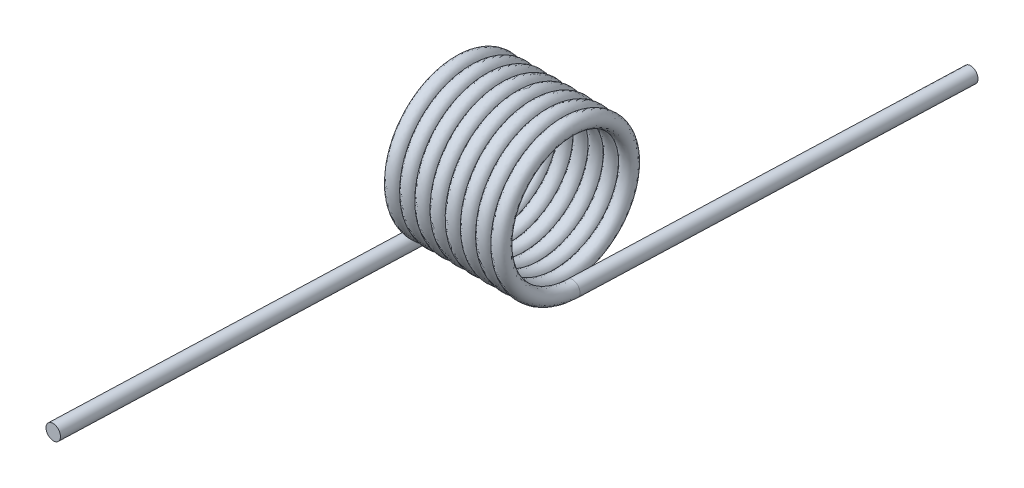
SolidWorks part; units mm, degrees
ref_plane "Front" through (0, 0, 0) normal (0, 0, 1) x (1, 0, 0)
ref_plane "Top" through (0, 0, 0) normal (0, 1, 0) x (1, 0, 0)
ref_plane "Right" through (0, 0, 0) normal (1, 0, 0) x (0, 0, -1)
sketch "Sketch1" plane through (0, 0, 0) normal (1, 0, 0) x (0, 0, -1)
  line L0 (0, 0) -> (0, -7.9375) construction
  line L1 (0, -7.9375) -> (0, -8.9281) construction
  line L2 (0, -8.9281) -> (0, -9.9187) construction
  circle A0 centre (0, 0) radius 7.9375 construction
  circle A1 centre (0, 0) radius 9.9187 construction
  circle A2 centre (0, 0) radius 8.9281
  circle A3 centre (0, -8.9281) radius 0.9906 construction
  circle A4 centre (0, 0) radius 6.35 construction
curve "Helix/Spiral1" pitch 2.0066 height 16.0528 radius 8.9281 centre (0, 0, 0) axis (1, 0, 0) start towards (0, 0, -1)
ref_plane "Plane1" through (0, -8.9281, 0) normal (0.0357, 0, -0.9994) x (-0.9994, 0, -0.0357)
sketch "Sketch2" plane through (0, -8.9281, 0) normal (0.0357, 0, -0.9994) x (-0.9994, 0, -0.0357)
  circle A0 centre (0, 0) radius 0.9906
  dimension "D1" = 1.9812
sweep "Sweep1" add profiles "Sketch2" path "Helix/Spiral1"
sketch "Sketch3" plane through (0, 0, 0) normal (-0.0357, 0, 0.9994) x (0.9994, 0, 0.0357)
  circle A1 centre (0, -8.9281) radius 0.9906
  circle A2 centre (0, -8.9281) radius 0.9906
  dimension "D1" = 0
extrude "Extrude1" add sketch "Sketch3" along normal blind 50.8
sketch "Sketch4" plane through (0.0205, 0, -0.5735) normal (0.0357, 0, -0.9994) x (-0.9957, -0.0856, -0.0356)
  circle A1 centre (-15.2194, -10.2686) radius 0.9906
  circle A2 centre (-15.2194, -10.2686) radius 0.9906
  dimension "D1" = 0
extrude "Extrude2" add sketch "Sketch4" along normal blind 50.8
sketch "Sketch5" plane through (0, 0, 0) normal (1, 0, 0) x (0, 0, -1)
  circle A0 centre (0, 0) radius 6.35 construction
  circle A1 centre (0, 0) radius 6.35
ref_plane "Plane2" through (0, 0, 0) normal (1, 0, 0) x (0, 0, -1)
ref_axis "Axis1" through (0, 0, 0) along (1, 0, 0)
equation "\"D4@Helix/Spiral1\"=\"Wire Dia@Sketch1\"+.001"
equation "\"D1@Sketch2\"=\"Wire Dia@Sketch1\""
equation "\"D1@Extrude2\"=\"Leg Length@Extrude1\""
